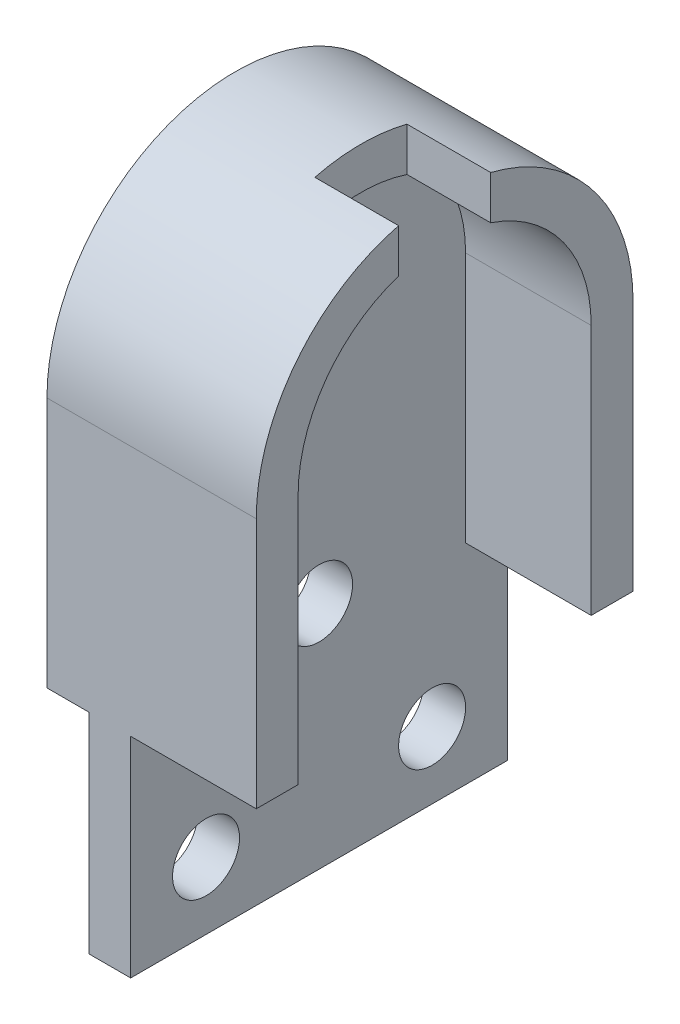
SolidWorks part; units mm, degrees
ref_plane "Спереди" through (0, 0, 0) normal (0, 0, 1) x (1, 0, 0)
ref_plane "Сверху" through (0, 0, 0) normal (0, 1, 0) x (1, 0, 0)
ref_plane "Справа" through (0, 0, 0) normal (1, 0, 0) x (0, 0, -1)
sketch "Эскиз1" plane through (0, 0, 0) normal (1, 0, 0) x (0, 0, -1)
  line L0 (-17.5, 27.5) -> (-17.5, -2.5)
  line L1 (-22.5, -27.5) -> (22.5, -27.5)
  line L2 (-22.5, -27.5) -> (-22.5, 27.5)
  line L3 (-22.5, 27.5) -> (22.5, 27.5)
  line L4 (22.5, -27.5) -> (22.5, 27.5)
  line L5 (-22.5, -27.5) -> (22.5, 27.5) construction
  line L6 (-22.5, 27.5) -> (22.5, -27.5) construction
  line L7 (-17.5, -2.5) -> (-22.5, -2.5)
  line L8 (17.5, 27.5) -> (17.5, -2.5)
  line L9 (17.5, -2.5) -> (22.5, -2.5)
  arc A0 (17.5, 27.5) -> (-17.5, 27.5) centre (0, 27.5) ccw
  arc A1 (22.5, 27.5) -> (-22.5, 27.5) centre (0, 27.5) ccw
  point P0 (0, 0)
  dimension "D1" = 45
  dimension "D2" = 55
  dimension "D4" = 30
  dimension "D3" = 5
extrude "Бобышка-Вытянуть1" add sketch "Эскиз1" along normal blind 5 contours L9 L8 L3 L0 L7 L2 L1 L4 | L7 L0 L3 L2 | L3 A1 A0 | L3 A0 | L8 L9 L4 L3 region at (0, -1.7241, 0) region at (0, 12.5, 20) region at (0, 34.9272, 0) region at (0, 28.0031, 20) region at (0, 12.5, -20)
extrude "Бобышка-Вытянуть2" add sketch "Эскиз1<3>" along normal blind 20 and the other way blind 5 contours L3 A1 A0 | L7 L0 L3 L2 | L8 L9 L4 L3 region at (0, 12.5, 20) region at (0, 28.0031, 20) region at (0, 12.5, -20)
sketch "Эскиз1<3>" plane through (0, 0, 0) normal (1, 0, 0) x (0, 0, -1) same geometry as "Эскиз1"
sketch "Эскиз3" plane through (5, 0, 0) normal (1, 0, 0) x (0, 0, -1)
  line L0 (-22.5, -27.5) -> (-22.5, -2.5) construction
  line L1 (22.5, -27.5) -> (22.5, -2.5) construction
  line L2 (-22.5, -27.5) -> (22.5, -27.5) construction
  circle A0 centre (-13.5, -19.5) radius 4
  circle A1 centre (13.5, -19.5) radius 4
  circle A2 centre (0, 0) radius 4
  dimension "D1" = 8
  dimension "D2" = 9
  dimension "D3" = 9
  dimension "D4" = 8
extrude "Вырез-Вытянуть2" cut sketch "Эскиз3" against normal through all
sketch "Эскиз5" plane through (20, 0, 0) normal (1, 0, 0) x (0, 0, -1)
  line L0 (0, 50) -> (0, 45) construction
  line L2 (-5.5, 40) -> (5.5, 40)
  line L3 (-5.5, 40) -> (-5.5, 55)
  line L4 (-5.5, 55) -> (5.5, 55)
  line L5 (5.5, 40) -> (5.5, 55)
  line L6 (-5.5, 40) -> (5.5, 55) construction
  line L7 (-5.5, 55) -> (5.5, 40) construction
  arc A1 (22.5, 27.5) -> (-22.5, 27.5) centre (0, 27.5) ccw construction
  arc A2 (17.5, 27.5) -> (-17.5, 27.5) centre (0, 27.5) ccw construction
  point P9 (0, 47.5)
  dimension "D1" = 11
  dimension "D2" = 15
extrude "Вырез-Вытянуть3" cut sketch "Эскиз5" against normal blind 10
